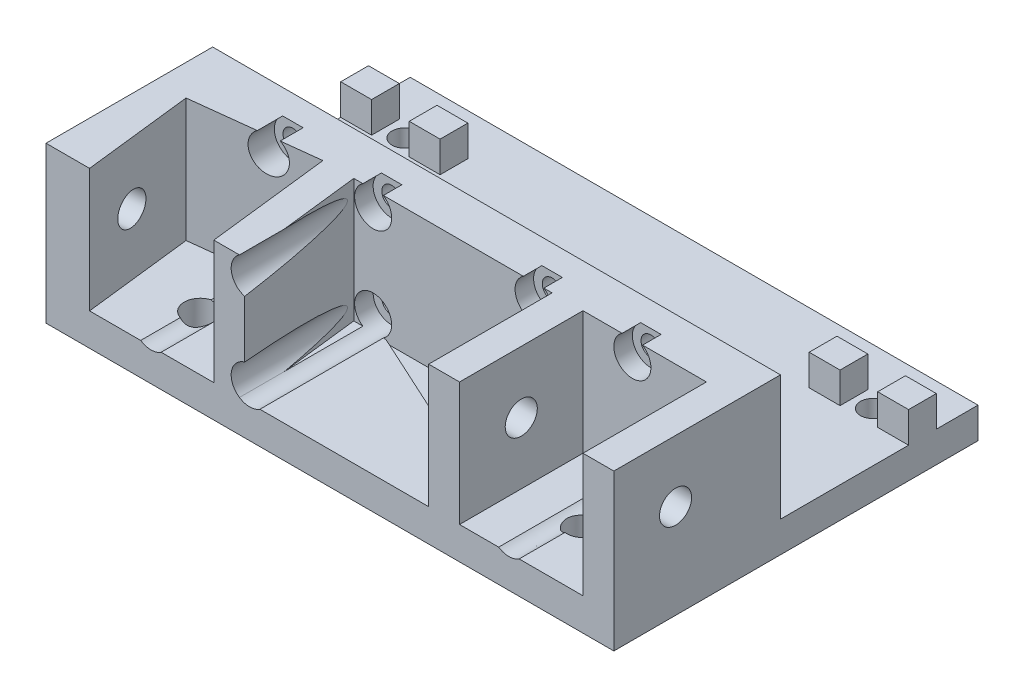
SolidWorks part; units mm, degrees
ref_plane "Front" through (0, 0, 0) normal (0, 0, 1) x (1, 0, 0)
ref_plane "Top" through (0, 0, 0) normal (0, 1, 0) x (1, 0, 0)
ref_plane "Right" through (0, 0, 0) normal (1, 0, 0) x (0, 0, -1)
other "Configuration Table"
sketch "Sketch1" plane through (0, 0, 0) normal (0, 0, 1) x (1, 0, 0)
  line L1 (-20, -10) -> (20, -10)
  line L2 (-20, -10) -> (-20, 10)
  line L3 (-20, 10) -> (20, 10)
  line L4 (20, -10) -> (20, 10)
  line L5 (-20, -10) -> (20, 10) construction
  line L6 (-20, 10) -> (20, -10) construction
  line L7 (-8, -7.5) -> (8, -7.5) construction
  line L8 (-8, -7.5) -> (-8, 7.5) construction
  line L9 (-8, 7.5) -> (8, 7.5) construction
  line L10 (8, -7.5) -> (8, 7.5) construction
  line L11 (-8, -7.5) -> (8, 7.5) construction
  line L12 (-8, 7.5) -> (8, -7.5) construction
  circle A0 centre (-8, 7.5) radius 1.6
  circle A1 centre (8, 7.5) radius 1.6
  circle A2 centre (8, -7.5) radius 1.6
  circle A3 centre (-8, -7.5) radius 1.6
  point P0 (0, 0)
  point P6 (0, 0)
extrude "Boss-Extrude1" add sketch "Sketch1" along normal blind 7
sketch "Sketch2" plane through (20, 0, 0) normal (1, 0, 0) x (0, 0, -1)
  line L0 (0, 0) -> (0, 5) construction
  line L1 (0, -10) -> (0, 10) construction
  line L2 (0, 0) -> (0, -5) construction
  line L3 (0, -5) -> (3, -5) construction
  line L4 (3, -5) -> (3, 5)
  line L5 (3, 5) -> (0, 5) construction
  line L6 (0, -10) -> (9.5, -10)
  line L7 (0, 10) -> (9.5, 10)
  line L8 (9.5, 10) -> (9.5, 5)
  line L9 (9.5, 5) -> (3, 5)
  line L10 (9.5, -10) -> (9.5, -5)
  line L11 (9.5, -5) -> (3, -5)
  line L12 (0, -10) -> (0, -5) construction
  line L13 (0, 5) -> (0, 10) construction
  line L14 (0, -10) -> (-7, -10)
  line L15 (-7, -10) -> (-7, 10)
  line L16 (-7, 10) -> (0, 10)
extrude "Boss-Extrude2" add sketch "Sketch2" along normal blind 5
sketch "Sketch3" plane through (-20, 0, 0) normal (-1, 0, 0) x (0, 0, 1)
  line L0 (7, 10) -> (-9.5, 10)
  line L1 (-9.5, 10) -> (-9.5, 5)
  line L2 (-9.5, 5) -> (-3, 5)
  line L3 (-3, 5) -> (-3, -5)
  line L4 (-3, -5) -> (-9.5, -5)
  line L5 (-9.5, -5) -> (-9.5, -10)
  line L6 (-9.5, -10) -> (7, -10)
  line L7 (7, -10) -> (7, 10)
extrude "Boss-Extrude3" add sketch "Sketch3" along normal blind 5
sketch "Sketch4" plane through (0, -10, 0) normal (0, -1, 0) x (1, 0, 0)
  line L0 (-25, 7) -> (-25, -9.5)
  line L1 (-25, -9.5) -> (-20, -9.5)
  line L2 (-20, -9.5) -> (-20, 0)
  line L3 (-20, 0) -> (20, 0)
  line L4 (20, 0) -> (20, -9.5)
  line L5 (20, -9.5) -> (25, -9.5)
  line L6 (25, -9.5) -> (25, 7)
  line L7 (25, 7) -> (-25, 7)
extrude "Boss-Extrude4" add sketch "Sketch4" along normal blind 0.25
sketch "Sketch5" plane through (0, -10.25, 0) normal (0, -1, 0) x (1, 0, 0)
  line L0 (-20, 0) -> (-20, -29) construction
  line L1 (-25, 7) -> (-25, -29)
  line L2 (25, 7) -> (25, -29)
  line L3 (25, -29) -> (-25, -29)
  line L4 (-25, 7) -> (25, 7)
extrude "Boss-Extrude5" add sketch "Sketch5" along normal blind 5
sketch "Sketch6" plane through (0, 0, 7) normal (0, 0, 1) x (1, 0, 0)
  circle A0 centre (-8, 7.5) radius 3
  circle A1 centre (-8, -7.5) radius 3
  circle A2 centre (8, -7.5) radius 3
  circle A3 centre (8, 7.5) radius 3
extrude "Cut-Extrude1" cut sketch "Sketch6" against normal blind 3
sketch "Sketch7" plane through (-25, 0, 0) normal (-1, 0, 0) x (0, 0, 1)
  line L0 (-3, -5) -> (7, -5)
  line L1 (7, -15.25) -> (7, 10) construction
  line L2 (7, -5) -> (7, -15.25)
  line L3 (7, -15.25) -> (-29, -15.25)
  line L4 (-29, -15.25) -> (-29, -10.25)
  line L5 (-29, -10.25) -> (-9.5, -10.25)
  line L6 (-9.5, -10.25) -> (-9.5, -5)
  line L7 (-9.5, -5) -> (-3, -5)
extrude "Boss-Extrude6" add sketch "Sketch7" along normal blind 20
sketch "Sketch9" plane through (0, 0, 7) normal (0, 0, 1) x (1, 0, 0)
  line L0 (0, 0) -> (20, 0) construction
  line L1 (0, 0) -> (0, 10)
  line L2 (-20, 0) -> (-20, 10) construction
  line L3 (20, 0) -> (20, 10)
  line L4 (-20, 0) -> (-20, -10) construction
  line L5 (20, 0) -> (20, -10)
  line L6 (20, -10) -> (25, -10)
  line L7 (25, 10) -> (25, -15.25) construction
  line L8 (25, -10) -> (25, 10)
  line L9 (25, 10) -> (20, 10)
  line L10 (-20, 10) -> (-25, 10) construction
  line L11 (-25, 10) -> (-25, -10) construction
  line L12 (-25, -10) -> (-20, -10) construction
  line L13 (0, 0) -> (0, -10)
  line L14 (0, 10) -> (-5, 10)
  line L15 (-5, 10) -> (-5, -10)
  line L16 (-5, -10) -> (0, -10)
extrude "Boss-Extrude8" add sketch "Sketch9" along normal blind 20
sketch "Sketch10" plane through (-25, 0, 0) normal (-1, 0, 0) x (0, 0, 1)
  line L0 (0, 0) -> (7, 0) construction
  line L1 (7, 0) -> (7, -5) construction
  line L2 (7, 0) -> (17, 0) construction
  circle A0 centre (17, 0) radius 2.6
extrude "Cut-Extrude2" cut sketch "Sketch10" against normal through all
sketch "Sketch11" plane through (0, 0, 7) normal (0, 0, 1) x (1, 0, 0)
  line L0 (-9.6583, 10) -> (-25, 10) construction
  line L2 (10, -10) -> (10, 10) construction
  line L3 (10, 10) -> (-10, 10) construction
  line L4 (-10, -10) -> (-10, 10) construction
  line L5 (10, -10) -> (-10, 10) construction
  line L6 (10, 10) -> (-10, -10) construction
  line L11 (25, -15.25) -> (25, -10)
  line L12 (25, -10) -> (10, -10)
  line L13 (10, -10) -> (9.6583, -10)
  line L15 (-9.6583, -10) -> (9.6583, -10) construction
  line L17 (6.3417, -10) -> (-5, -10)
  line L18 (-5, -10) -> (-5, -15.25)
  line L19 (25, -15.25) -> (-45, -15.25) construction
  line L20 (-5, -15.25) -> (25, -15.25)
  circle A0 centre (8, -7.5) radius 3 construction
  circle A1 centre (-8, -7.5) radius 3 construction
  circle A2 centre (8, -7.5) radius 3 construction
  spline S0 degree 3 poles (9.6583, -10) (9.1046, -10.3723) (7.8997, -10.6752) (6.7571, -10.2766) (6.3417, -10) knots 0 0 0 0 0.571534 1 1 1 1
  point P0 (0, 0)
extrude "Boss-Extrude9" add sketch "Sketch11" along normal through all
sketch "Sketch12" plane through (0, -15.25, 0) normal (0, -1, 0) x (1, 0, 0)
  line L0 (-5, 17) -> (25, 17) construction
  line L1 (-5, 27) -> (-5, 7) construction
  line L2 (25, -29) -> (25, 27) construction
  circle A0 centre (10, 17) radius 2.6
extrude "Cut-Extrude3" cut sketch "Sketch12" against normal through all
sketch "Sketch13" plane through (0, 0, -9.5) normal (0, 0, -1) x (-1, 0, 0)
  line L1 (20, 10) -> (25, 10)
  line L2 (20, 10) -> (20, 5)
  line L3 (20, 5) -> (25, 5)
  line L4 (25, 10) -> (25, 5)
  line L5 (-20, 5) -> (-25, 5)
  line L6 (-20, 5) -> (-20, 10)
  line L7 (-20, 10) -> (-25, 10)
  line L8 (-25, 5) -> (-25, 10)
extrude "Cut-Extrude4" cut sketch "Sketch13" against normal up to surface (6.5 mm away) up to face at (22.5, 0, -3)
chamfer "Chamfer1" distance 10 angle 57 1 edges at (-25, -5, 2) first distance on face at (-30, -5, -1.8333)
sketch "Sketch14" plane through (0, 0, 0) normal (0, 0, -1) x (-1, 0, 0)
  line L0 (20, 10) -> (21, 10)
  line L1 (25.2589, 10) -> (20, 10) construction
  line L2 (21, 10) -> (21, -10.25)
  line L3 (45, -10.25) -> (20, -10.25) construction
  line L4 (21, -10.25) -> (20, -10.25)
  line L5 (20, -10.25) -> (20, 10)
  line L6 (-20, 10) -> (-21, 10)
  line L7 (-20, 10) -> (-25, 10) construction
  line L8 (-21, 10) -> (-21, -10.25)
  line L9 (45, -10.25) -> (-25, -10.25) construction
  line L10 (-20, -10.25) -> (-25, -10.25) construction
  line L11 (-21, -10.25) -> (-20, -10.25)
  line L12 (-20, -10.25) -> (-20, 10)
extrude "Cut-Extrude5" cut sketch "Sketch14" along normal blind 10
sketch "Sketch16" plane through (0, 0, 0) normal (0, 0, -1) x (-1, 0, 0)
  line L0 (-21, 10) -> (-21, -10.25)
  line L1 (-21, -10.25) -> (-25, -10.25)
  line L2 (-25, -10.25) -> (-25, 10)
  line L3 (-25, 10) -> (-21, 10)
extrude "Cut-Extrude7" cut sketch "Sketch16" along normal blind 10
sketch "Sketch17" plane through (0, -15.25, 0) normal (0, -1, 0) x (1, 0, 0)
  line L0 (-5, 27) -> (-45, 7)
  line L1 (-45, 7) -> (-5, 7)
  line L2 (-5, 7) -> (-5, 27)
extrude "Boss-Extrude10" add sketch "Sketch17" against normal blind 4.75
sketch "Sketch18" plane through (0, 0, -29) normal (0, 0, -1) x (-1, 0, 0)
  line L0 (45, -15.25) -> (-25, -15.25)
  line L1 (-25, -15.25) -> (-25, -10.25)
  line L2 (-25, -10.25) -> (45, -10.25)
  line L3 (45, -10.25) -> (45, -15.25)
extrude "Boss-Extrude11" add sketch "Sketch18" along normal blind 3
sketch "Sketch19" plane through (0, 0, 0) normal (0, 0, -1) x (-1, 0, 0)
  line L1 (21, -10.25) -> (48.6351, -10.25)
  line L2 (21, -10.25) -> (21, 12.6094)
  line L3 (21, 12.6094) -> (48.6351, 12.6094)
  line L4 (48.6351, -10.25) -> (48.6351, 12.6094)
extrude "Cut-Extrude8" cut sketch "Sketch19" along normal blind 10
sketch "Sketch20" plane through (0, 0, 0) normal (0, 0, -1) x (-1, 0, 0)
  line L0 (0, 0) -> (42, 0) construction
  line L1 (-19.95, 10) -> (19.95, 10) construction
  line L2 (-19.95, 10) -> (-19.95, -10) construction
  line L3 (-19.95, -10) -> (19.95, -10) construction
  line L4 (19.95, 10) -> (19.95, -10) construction
  line L5 (-19.95, 10) -> (19.95, -10) construction
  line L6 (-19.95, -10) -> (19.95, 10) construction
  line L7 (61.95, 0) -> (67, 0) construction
  line L8 (22.05, 10) -> (61.95, 10) construction
  line L9 (22.05, 10) -> (22.05, -10) construction
  line L10 (22.05, -10) -> (61.95, -10) construction
  line L11 (61.95, 10) -> (61.95, -10) construction
  line L12 (22.05, 10) -> (61.95, -10) construction
  line L13 (22.05, -10) -> (61.95, 10) construction
  line L14 (25.2589, 10) -> (67, 10)
  line L15 (67, 10) -> (67, -15.25)
  line L16 (67, -15.25) -> (45, -15.25)
  line L17 (45, -15.25) -> (25.2589, -15.25)
  line L18 (-25, -15.25) -> (45, -15.25) construction
  line L19 (25.2589, -15.25) -> (25.2589, 10)
  line L21 (34, -7.5) -> (50, -7.5) construction
  line L22 (34, -7.5) -> (34, 7.5) construction
  line L23 (34, 7.5) -> (50, 7.5) construction
  line L24 (50, -7.5) -> (50, 7.5) construction
  line L25 (34, -7.5) -> (50, 7.5) construction
  line L26 (34, 7.5) -> (50, -7.5) construction
  circle A0 centre (34, 7.5) radius 1.6
  circle A1 centre (50, 7.5) radius 1.6
  circle A2 centre (50, -7.5) radius 1.6
  circle A3 centre (34, -7.5) radius 1.6
  point P0 (0, 0)
extrude "Boss-Extrude12" add sketch "Sketch20" against normal up to surface (7 mm away) up to face at (-5.3425, 9.2229, 7)
sketch "Sketch21" plane through (0, 0, 0) normal (0, 0, -1) x (-1, 0, 0)
  line L0 (34, 7.5) -> (50, -7.5) construction
  line L1 (50, -7.5) -> (34, -7.5) construction
  line L2 (34, -7.5) -> (34, 7.5) construction
  circle A0 centre (34, -7.5) radius 1.6
extrude "Cut-Extrude9" cut sketch "Sketch21" against normal blind 10
sketch "Sketch22" plane through (0, -10, 0) normal (0, 1, 0) x (1, 0, 0)
  line L0 (0, -7) -> (0, -407)
  line L1 (-65.9364, -22.6218) -> (-80.0764, -22.6218) construction
  line L2 (-80.0764, -22.6218) -> (-80.0764, -36.7618) construction
  line L3 (-80.0764, -36.7618) -> (-65.9364, -22.6218) construction
  line L4 (-67, -7) -> (-90.6392, -7) construction
  line L5 (-67, -7) -> (-62, -7)
  line L6 (-9.6583, -7) -> (-67, -7) construction
  line L7 (-34.8089, -27) -> (-37.1338, -7)
  line L8 (-62, -27) -> (-62, -7) construction
  line L10 (-67, -7) -> (-67, -27)
  line L11 (-67, -27) -> (-62, -27)
  line L12 (-62, -9.3093) -> (-27.3599, -307.3027) construction
  line L13 (-27.3599, -307.3027) -> (-7.4937, -304.9934) construction
  line L14 (-62, -9.3093) -> (-42.1338, -7)
  line L15 (-42.1338, -7) -> (-7.4937, -304.9934) construction
  line L16 (-42.1338, -18.5234) -> (-42.1338, -7) construction
  line L17 (-42.1338, -7) -> (-19.2255, -35.192) construction
  line L18 (-42.1338, -7) -> (-39.8089, -27)
  line L19 (-39.8089, -27) -> (-34.8089, -27)
  line L20 (-45, -7) -> (-8, -7) construction
  line L21 (-37.1338, -7) -> (-42.1338, -7)
  line L22 (-42.1338, -7) -> (-62, -7)
  line L23 (-62, -27) -> (-59.9436, -27)
  line L24 (-59.9436, -27) -> (-62, -9.3093)
extrude "Boss-Extrude13" add sketch "Sketch22" along normal up to surface (20 mm away) contours L7 L21 L18 L19 | L23 L24 L14 L22 L5 L10 L11 region at (-38.4713, -10, 17) region at (-62.6067, -10, 16.0286) up to face at (-3, 10, 10)
sketch "Sketch23" plane through (0, -15.25, 0) normal (0, -1, 0) x (1, 0, 0)
  line L0 (-5, 27) -> (-67, 27)
  line L1 (-67, 27) -> (-67, 7)
  line L4 (-67, 7) -> (-38.6774, 3.9036)
  line L5 (-38.6774, 3.9036) -> (-3.5029, 20.0478)
  line L6 (-3.5029, 20.0478) -> (-5, 27)
extrude "Boss-Extrude16" add sketch "Sketch23" against normal up to surface (5.25 mm away) up to face at (-59.6155, -10, 15.4619)
sketch "Sketch24" plane through (0, 0, 7) normal (0, 0, 1) x (1, 0, 0)
  circle A0 centre (-34, 7.5) radius 3
  circle A1 centre (-50, 7.5) radius 3
  circle A2 centre (-50, -7.5) radius 3
  circle A3 centre (-34, -7.5) radius 3
extrude "Cut-Extrude10" cut sketch "Sketch24" against normal up to surface (3 mm away) and the other way blind 30 up to face at (-6.4, 7.5, 4)
sketch "Sketch25" plane through (0, -10, 0) normal (0, 1, 0) x (1, 0, 0)
  line L0 (-62, -9.3093) -> (-42.1338, -7) construction
  line L1 (-52.0669, -8.1547) -> (-50.9122, -18.0878) construction
  circle A0 centre (-50.9122, -18.0878) radius 2.6
extrude "Cut-Extrude11" cut sketch "Sketch25" against normal blind 13
sketch "Sketch26" plane through (-62.2411, 0, 7.2352) normal (0.9933, 0, -0.1155) x (-0.1155, 0, -0.9933)
  line L0 (-2.0881, -10) -> (-2.0881, 10) construction
  line L1 (-2.0881, 0) -> (-12.0881, 0) construction
  circle A0 centre (-12.0881, 0) radius 2.6
extrude "Cut-Extrude12" cut sketch "Sketch26" against normal blind 13
sketch "Sketch27" plane through (0, 0, 0) normal (0, 0, -1) x (-1, 0, 0)
  line L0 (45, -10.25) -> (67, -10.25)
  line L1 (67, -15.25) -> (67, 10) construction
  line L2 (67, -10.25) -> (67, -15.25)
  line L3 (67, -15.25) -> (45, -15.25)
  line L4 (45, -15.25) -> (45, -10.25)
extrude "Boss-Extrude17" add sketch "Sketch27" along normal up to surface (32 mm away) up to face at (-10, -12.75, -32)
sketch "Sketch8" plane through (0, -10.25, 0) normal (0, 1, 0) x (1, 0, 0)
  line L0 (20, 23) -> (25, 23) construction
  line L1 (-56, 18.1812) -> (14, 18.1812) construction
  line L2 (20, 22.25) -> (20, 25.25) construction
  line L3 (20, 20.75) -> (20, 25.25)
  line L4 (-67, 18.1812) -> (-73.6716, 12.6916) construction
  line L5 (20, 20.75) -> (22, 20.75)
  line L8 (20, 23) -> (13.9, 23) construction
  line L9 (13.9, 23) -> (13.9, 20.75)
  line L10 (13.9, 20.75) -> (11.9, 20.75)
  line L14 (-67, 32) -> (-67, 0) construction
  line L15 (-21, 18.1812) -> (-21, 25.1041) construction
  line L16 (-62, 23) -> (-55.9, 23) construction
  line L17 (-62, 23) -> (-67, 23) construction
  line L27 (13.9, 23) -> (13.9, 25.25)
  line L28 (13.9, 25.25) -> (8.9, 25.25)
  line L29 (20, 25.25) -> (25, 25.25)
  line L30 (25, 25.25) -> (25, 20.75)
  line L31 (25, 20.75) -> (22, 20.75)
  line L32 (11.9, 20.75) -> (8.9, 20.75)
  line L33 (8.9, 20.75) -> (8.9, 25.25)
  line L34 (-50.9, 20.75) -> (-50.9, 25.25)
  line L35 (-53.9, 20.75) -> (-50.9, 20.75)
  line L36 (-67, 20.75) -> (-64, 20.75)
  line L37 (-67, 25.25) -> (-67, 20.75)
  line L38 (-62, 25.25) -> (-67, 25.25)
  line L39 (-55.9, 25.25) -> (-50.9, 25.25)
  line L40 (-55.9, 23) -> (-55.9, 25.25)
  line L41 (-55.9, 20.75) -> (-53.9, 20.75)
  line L42 (-55.9, 23) -> (-55.9, 20.75)
  line L43 (-62, 20.75) -> (-64, 20.75)
  line L44 (-62, 20.75) -> (-62, 25.25)
  line L45 (-67, 18.1812) -> (-67, 20.75) construction
  point P10 (20, 23)
  point P37 (-62, 23)
extrude "Boss-Extrude7" add sketch "Sketch8" along normal blind 5
sketch "Sketch15" plane through (0, -10.25, 0) normal (0, 1, 0) x (1, 0, 0)
  line L0 (20, 23) -> (13.9, 23) construction
  line L2 (20, 25.25) -> (20, 20.75) construction
  line L3 (-33.9, 19.95) -> (-40, 20) construction
  line L4 (13.9, 20.75) -> (13.9, 25.25) construction
  line L5 (13.9, 23) -> (-55.9, 23) construction
  line L6 (-55.9, 25.25) -> (-55.9, 20.75) construction
  line L7 (-55.9, 23) -> (-62, 23) construction
  line L8 (-62, 20.75) -> (-62, 25.25) construction
  circle A0 centre (16.95, 23) radius 2
  circle A1 centre (-58.95, 23) radius 2
extrude "Cut-Extrude6" cut sketch "Sketch15" against normal blind 10
